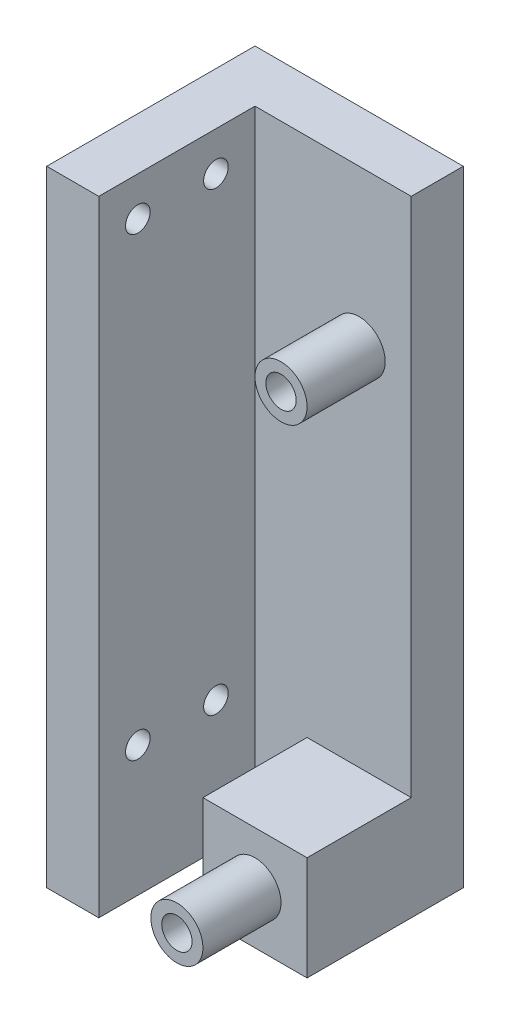
SolidWorks part; units mm, degrees
ref_plane "Front Plane" through (0, 0, 0) normal (0, 0, 1) x (1, 0, 0)
ref_plane "Top Plane" through (0, 0, 0) normal (0, 1, 0) x (1, 0, 0)
ref_plane "Right Plane" through (0, 0, 0) normal (1, 0, 0) x (0, 0, -1)
sketch "Sketch1" plane through (0, 0, 0) normal (0, 0, 1) x (1, 0, 0)
  line L1 (0, 0) -> (25.4, 0)
  line L2 (0, 0) -> (0, 76.2)
  line L3 (0, 76.2) -> (25.4, 76.2)
  line L4 (25.4, 0) -> (25.4, 76.2)
  dimension "D1" = 76.2
  dimension "D2" = 25.4
extrude "Boss-Extrude1" add sketch "Sketch1" against normal blind 25.4
sketch "Sketch10" plane through (25.4, 0, 0) normal (1, 0, 0) x (0, 0, -1)
  line L0 (25.4, 76.2) -> (0, 76.2) construction
  line L1 (19.05, 76.2) -> (0, 76.2)
  line L2 (19.05, 76.2) -> (19.05, 0)
  line L3 (19.05, 0) -> (0, 0)
  line L4 (0, 76.2) -> (0, 0)
  line L5 (25.4, 0) -> (0, 0) construction
  line L6 (25.4, 0) -> (25.4, 76.2) construction
  line L8 (0, 0) -> (0, 76.2) construction
  dimension "D1" = 6.35
extrude "Cut-Extrude5" cut sketch "Sketch10" against normal offset from surface (19.05 mm away) 6.35 up to face at (0, 38.1, -12.7)
sketch "Sketch12" plane through (0, 0, -25.4) normal (0, 0, -1) x (-1, 0, 0)
  line L0 (-25.4, 76.2) -> (0, 76.2) construction
  line L1 (-25.4, 0) -> (-25.4, 76.2) construction
  circle A1 centre (-19.05, 57.15) radius 3.175
  circle A2 centre (-19.05, 57.15) radius 1.85
  dimension "D2" = 6.35
  dimension "D4" = 3.7
  dimension "D1" = 19.05
  dimension "D3" = 6.35
extrude "Boss-Extrude2" add sketch "Sketch12" against normal blind 9.525 from surface starting at face at (15.875, 38.1, -19.05)
sketch "Sketch13" plane through (0, 0, -25.4) normal (0, 0, -1) x (-1, 0, 0)
  line L1 (-25.4, 0) -> (-12.7, 0)
  line L3 (-25.4, 12.7) -> (-12.7, 12.7)
  line L4 (-12.7, 0) -> (-12.7, 12.7)
  line L5 (-25.4, 12.7) -> (-25.4, 0)
  point P7 (0, 0)
  point P8 (0, 0)
  dimension "D2" = 12.7
  dimension "D3" = 12.7
extrude "Boss-Extrude3" add sketch "Sketch13" against normal blind 12.7 from surface starting at face at (19.05, 60.325, -19.05)
sketch "Sketch14" plane through (0, 0, -6.35) normal (0, 0, 1) x (1, 0, 0)
  line L1 (25.4, 0) -> (12.7, 0) construction
  line L2 (25.4, 12.7) -> (25.4, 76.2) construction
  circle A0 centre (19.05, 6.35) radius 1.85
  circle A1 centre (19.05, 6.35) radius 3.175
  circle A3 centre (19.05, 57.15) radius 1.85 construction
  circle A4 centre (19.05, 57.15) radius 3.175 construction
  point P3 (0, 0)
  dimension "D1" = 6.35
  dimension "D2" = 6.35
extrude "Boss-Extrude4" add sketch "Sketch14" along normal blind 9.525
sketch "Sketch15" plane through (6.35, 0, 0) normal (1, 0, 0) x (0, 0, -1)
  line L1 (19.05, 76.2) -> (0, 76.2) construction
  line L2 (0, 76.2) -> (0, 0) construction
  line L3 (19.05, 12.7) -> (19.05, 76.2) construction
  line L4 (0, 0) -> (19.05, 0) construction
  line L5 (25.4, 0) -> (6.35, 0) construction
  circle A0 centre (4.7625, 71.4375) radius 1.5
  circle A1 centre (14.2875, 71.4375) radius 1.5
  circle A2 centre (4.7625, 15.875) radius 1.5
  circle A3 centre (14.2875, 15.875) radius 1.5
  point P8 (0, 0)
  point P9 (0, 0)
  point P10 (0, 0)
  dimension "D1" = 3
  dimension "D2" = 4.7625
  dimension "D3" = 4.7625
  dimension "D4" = 4.7625
  dimension "D5" = 15.875
  dimension "D6" = 15.875
extrude "Cut-Extrude6" cut sketch "Sketch15" against normal through all
equation "\"D4@Sketch12\"= 3.7mm"
equation "\"D1@Boss-Extrude1\"=(0.375+15.7mm)+0.25+0.25"
equation "\"tightTol\"= 0.005in"
equation "\"normTol\"= 0.01in"
equation "\"looseTol\"= 0.02in"
equation "\"D1@Sketch15\"=3mm"
